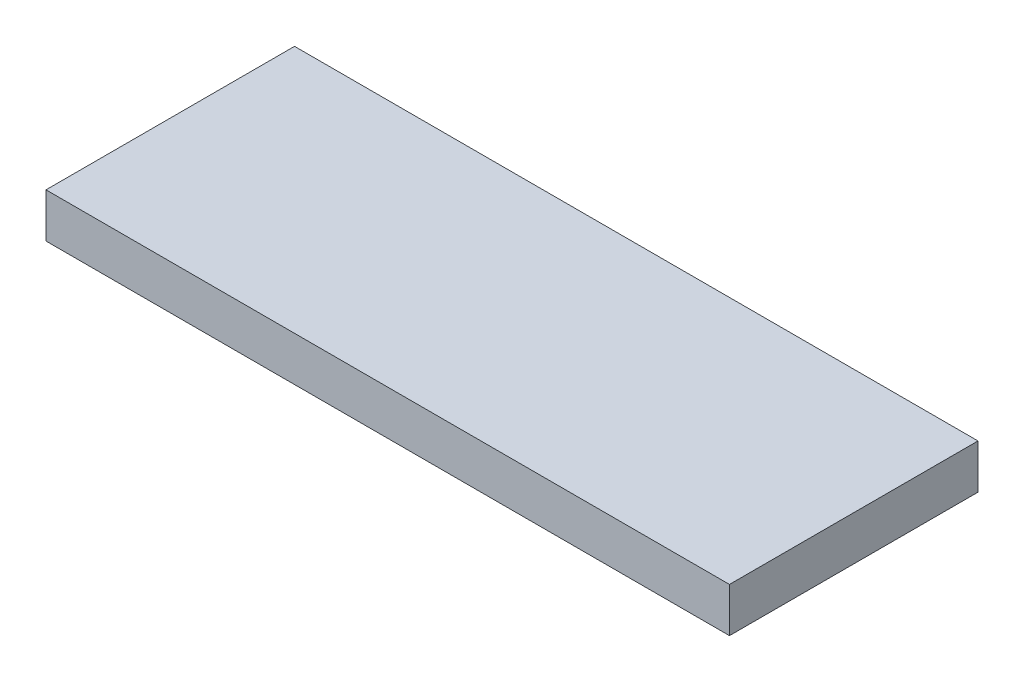
SolidWorks part; units mm, degrees
ref_plane "Front Plane" through (0, 0, 0) normal (0, 0, 1) x (1, 0, 0)
ref_plane "Top Plane" through (0, 0, 0) normal (0, 1, 0) x (1, 0, 0)
ref_plane "Right Plane" through (0, 0, 0) normal (1, 0, 0) x (0, 0, -1)
sketch "Sketch1" plane through (0, 0, 0) normal (0, 1, 0) x (1, 0, 0)
  line L1 (77, 28) -> (-77, 28)
  line L2 (77, 28) -> (77, -28)
  line L3 (77, -28) -> (-77, -28)
  line L4 (-77, 28) -> (-77, -28)
  line L5 (77, 28) -> (-77, -28) construction
  line L6 (77, -28) -> (-77, 28) construction
  point P0 (0, 0)
  dimension "D1" = 154
  dimension "D2" = 56
extrude "base" add sketch "Sketch1" along normal blind 10 contours L1 L4 L3 L2
sketch "Sketch2" plane through (0, 0, 0) normal (0, -1, 0) x (1, 0, 0)
  circle A0 centre (0, 0) radius 3
  dimension "D1" = 6
extrude "load cell button cut" [suppressed] cut sketch "Sketch2" against normal blind 2
sketch "Sketch4" plane through (0, 0, 0) normal (1, 0, 0) x (0, 0, -1)
  line L0 (3, 0) -> (3, 2)
  line L1 (3, 2) -> (0, 3.7321)
  line L2 (0, 3.7321) -> (0, 0) construction
  line L3 (0, 0) -> (3, 0)
  line L4 (0, 3.7321) -> (0, 0)
  dimension "D1" = 3
  dimension "D2" = 2
  dimension "D3" = 60
revolve "Cut-Revolve1" [suppressed] cut sketch "Sketch4" angle 360 about L2
equation "\"D2@Sketch1\"=46+10"
equation "\"D1@Sketch1\"=144+10"
